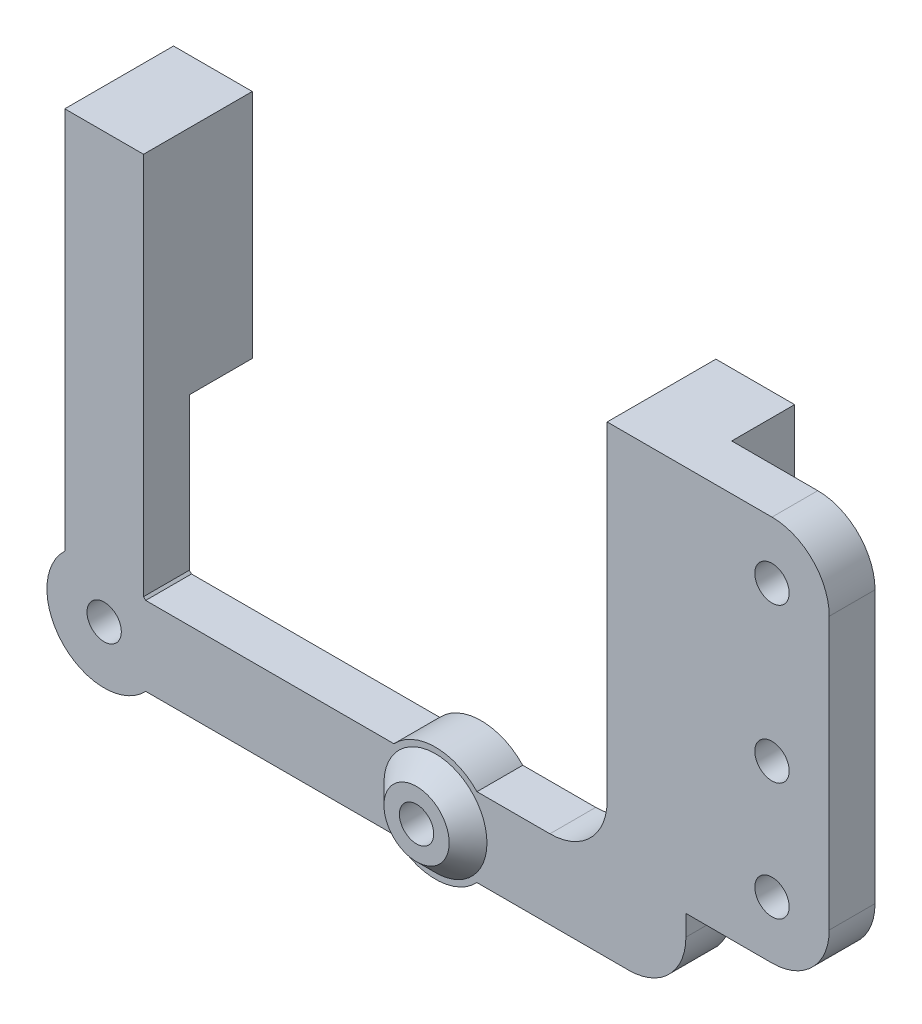
SolidWorks part; units mm, degrees
ref_plane "Alzado" through (0, 0, 0) normal (0, 0, 1) x (1, 0, 0)
ref_plane "Planta" through (0, 0, 0) normal (0, 1, 0) x (1, 0, 0)
ref_plane "Vista lateral" through (0, 0, 0) normal (1, 0, 0) x (0, 0, -1)
sketch "Croquis1" plane through (0, 0, 0) normal (0, 0, 1) x (1, 0, 0)
  line L0 (25.5, -3.4) -> (54.9, -3.4) construction
  line L1 (25.5, 10.1) -> (25.5, -16.9) construction
  line L2 (54.9, 1.74) -> (54.9, -8.54) construction
  line L3 (59.9, -8.54) -> (59.9, 15.2)
  line L4 (54.9, 20.2) -> (40.5, 20.2)
  line L8 (0, 20.2) -> (-6.88, 20.2)
  line L9 (-6.88, 20.2) -> (-6.88, -13.2714)
  line L17 (40.5, -8.46) -> (40.5, 20.2)
  line L18 (35.5, -13.46) -> (29.1286, -13.46)
  line L19 (0, 20.2) -> (0, -13.2714)
  line L20 (0.1886, -20.34) -> (21.8714, -20.34)
  line L21 (54.9, -13.54) -> (47.38, -13.54)
  line L22 (47.38, -13.54) -> (47.38, -15.34)
  line L23 (21.8714, -13.46) -> (0.1886, -13.46)
  line L24 (29.1286, -20.34) -> (42.38, -20.34)
  circle A0 centre (54.9, 1.74) radius 1.5
  circle A1 centre (54.9, -8.54) radius 1.5
  circle A2 centre (25.5, -16.9) radius 1.5
  arc A3 (21.8714, -20.34) -> (29.1286, -20.34) centre (25.5, -16.9) ccw
  arc A4 (-6.88, -13.2714) -> (0.1886, -20.34) centre (-3.44, -16.9) ccw
  arc A5 (54.9, -13.54) -> (59.9, -8.54) centre (54.9, -8.54) ccw
  arc A6 (59.9, 15.2) -> (54.9, 20.2) centre (54.9, 15.2) ccw
  arc A7 (0.1886, -13.46) -> (0, -13.2714) centre (-3.44, -16.9) ccw
  arc A8 (29.1286, -13.46) -> (21.8714, -13.46) centre (25.5, -16.9) ccw
  circle A9 centre (-3.44, -16.9) radius 1.5
  circle A10 centre (54.9, 15.2) radius 1.5
  arc A11 (35.5, -13.46) -> (40.5, -8.46) centre (35.5, -8.46) ccw
  arc A12 (42.38, -20.34) -> (47.38, -15.34) centre (42.38, -15.34) ccw
  point P28 (0, 0)
  dimension "D4" = 3
  dimension "D5" = 5
  dimension "D6" = 6.88
  dimension "D7" = 6.88
  dimension "D9" = 10
  dimension "D11" = 5
  dimension "D14" = 5
  dimension "D1" = 10.28
  dimension "D2" = 27
  dimension "D3" = 29.4
  dimension "D8" = 6.88
  dimension "D10" = 3.44
  dimension "D12" = 3.44
  dimension "D13" = 5
extrude "Saliente-Extruir1" add sketch "Croquis1" along normal blind 4
sketch "Croquis2" plane through (0, 0, 0) normal (0, 0, -1) x (-1, 0, 0)
  line L0 (-40.5, 20.2) -> (0, 20.2) construction
  line L1 (-40.5, 20.2) -> (-47.38, 20.2)
  line L2 (-40.5, 20.2) -> (-40.5, 0)
  line L3 (-40.5, 0) -> (-47.38, 0)
  line L4 (-47.38, 20.2) -> (-47.38, 0)
  line L5 (0, 0) -> (6.88, 0)
  line L6 (0, 0) -> (0, 20.2)
  line L7 (0, 20.2) -> (6.88, 20.2)
  line L8 (6.88, 0) -> (6.88, 20.2)
  point P14 (0, 0)
extrude "Saliente-Extruir2" add sketch "Croquis2" along normal up to surface (5.5 mm away)
sketch "Croquis3" plane through (0, 0, 4) normal (0, 0, 1) x (1, 0, 0)
  circle A0 centre (25.5, -16.9) radius 1.5
  circle A1 centre (25.5, -16.9) radius 2.5
  dimension "D1" = 3
  dimension "D2" = 5
extrude "Saliente-Extruir3" add sketch "Croquis3" along normal up to surface (1.65 mm away)
chamfer "Chaflán2" distance 2 angle 45 1 edges at (28, -16.9, 4)
sketch "Croquis4" plane through (0, 0, 0) normal (0, 0, -1) x (-1, 0, 0)
  circle A0 centre (-25.5, -16.9) radius 1.5
  circle A1 centre (-54.9, 1.74) radius 1.5
  circle A2 centre (-54.9, -8.54) radius 1.5
  point P9 (-54.9, -8.8535)
  point P10 (-54.9, -8.54)
  dimension "D1" = 3
extrude "Saliente-Extruir4" add sketch "Croquis4" against normal blind 1
sketch "Croquis5" plane through (0, 0, -5.5) normal (0, 0, -1) x (-1, 0, 0)
  circle A0 centre (-45.5, 5.4) radius 1.25
  circle A1 centre (-45.5, 14.8) radius 1.25
  circle A2 centre (5, 14.8) radius 1.25
  circle A3 centre (5, 5.4) radius 1.25
  dimension "D1" = 2.5
extrude "Cortar-Extruir1" cut sketch "Croquis5" against normal blind 8
